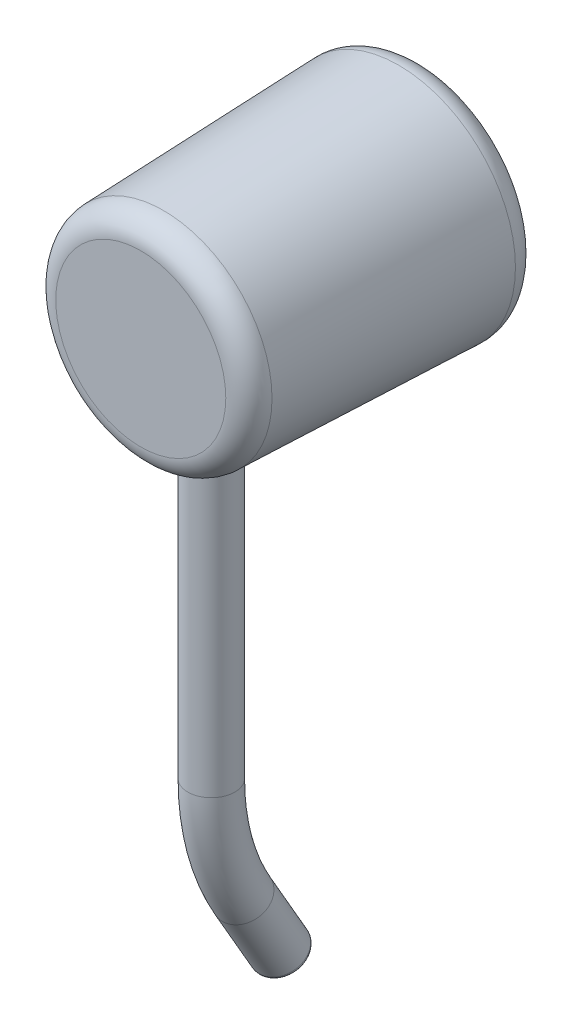
SolidWorks part; units mm, degrees
ref_plane "Front Plane" through (0, 0, 0) normal (1, 0, 0) x (0, 1, 0)
ref_plane "Top Plane" through (0, 0, 0) normal (0, 0, 1) x (0, 1, 0)
ref_plane "Right Plane" through (0, 0, 0) normal (0, 1, 0) x (-1, 0, 0)
sketch "Sketch1" plane through (0, 0, 0) normal (0, 0, 1) x (0, 1, 0)
  circle A0 centre (0, 0) radius 25
  dimension "D1" = 50
extrude "Boss-Extrude1" add sketch "Sketch1" along normal blind 60 draft 2
fillet "Fillet2" radius 5 2 edges at (22.9048, 0, 60) (25, 0, 0)
sketch "Sketch2" plane through (0, 0, 0) normal (1, 0, 0) x (0, 1, 0)
  line L0 (0, 45) -> (-86.6025, 45)
  line L1 (-111.6025, 38.3013) -> (-125.9808, 30)
  arc A0 (-86.6025, 45) -> (-111.6025, 38.3013) centre (-86.6025, -5) ccw
  point P7 (-100, 45)
  dimension "D5" = 50
  dimension "D1" = 45
  dimension "D2" = 100
  dimension "D3" = 150
  dimension "D4" = 30
sketch "Sketch3" plane through (0, 0, 0) normal (0, 1, 0) x (-1, 0, 0)
  circle A0 centre (0, 45) radius 5
  dimension "D1" = 10
sweep "Sweep1" add profiles "Sketch3" path "Sketch2"
fillet "Fillet4" radius 1 1 edges at (0, -128.4808, 34.3301)
fillet "Fillet6" radius 2.5 1 edges at (1.9408, -23.1866, 49.608)
sketch "Sketch4" plane through (0, -81.4952, -47.0513) normal (0, -0.866, -0.5) x (1, 0, 0)
  circle A0 centre (0, 88.9711) radius 2.5
  dimension "D1" = 5
extrude "Cut-Extrude1" cut sketch "Sketch4" against normal blind 5
